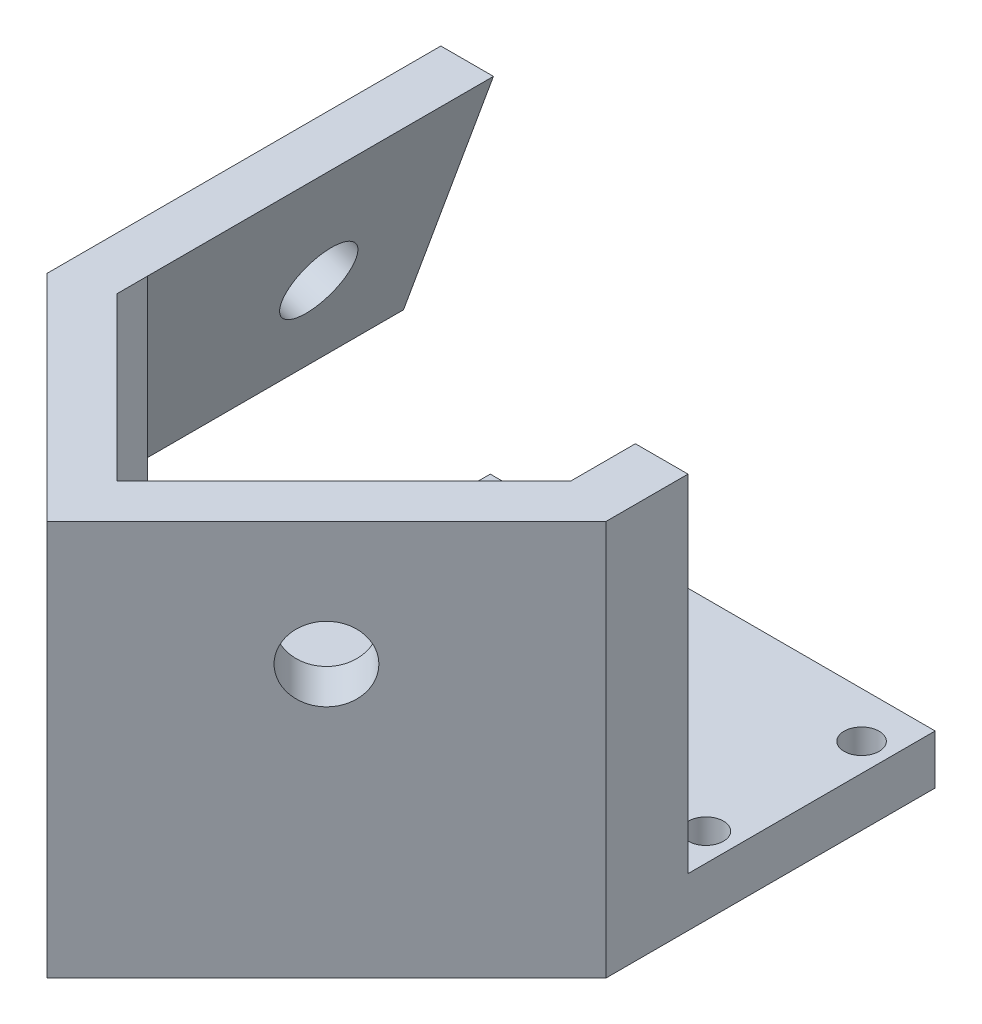
SolidWorks part; units mm, degrees
material "PLA Grey"
ref_plane "Front Plane" through (0, 0, 0) normal (0, 0, 1) x (1, 0, 0)
ref_plane "Top Plane" through (0, 0, 0) normal (0, 1, 0) x (1, 0, 0)
ref_plane "Right Plane" through (0, 0, 0) normal (1, 0, 0) x (0, 0, -1)
sketch "Sketch1" plane through (0, 0, 0) normal (0, 1, 0) x (1, 0, 0)
  line L0 (-35.921, 0) -> (0, 35.921)
  line L1 (-35.921, 0) -> (0, -35.921)
  line L2 (0, 35.921) -> (35.921, 0)
  line L3 (0, -35.921) -> (35.921, 0)
  line L4 (-35.921, 0) -> (35.921, 0) construction
  line L5 (0, 35.921) -> (0, -35.921) construction
  point P1 (0, 0)
  dimension "D1" = 50.8
  dimension "D2" = 50.8
extrude "Boss-Extrude1" add sketch "Sketch1" along normal mid plane 31.75
sketch "Sketch2" plane through (17.9605, 0, 17.9605) normal (0.7071, 0, 0.7071) x (0.7071, 0, -0.7071)
  circle A0 centre (0, 0) radius 4.7625
  dimension "D1" = 9.525
extrude "Cut-Extrude1" cut sketch "Sketch2" against normal blind 8
sketch "Sketch3" plane through (-17.9605, 0, 17.9605) normal (-0.7071, 0, 0.7071) x (0.7071, 0, 0.7071)
  circle A0 centre (0, 0) radius 4.7625
  dimension "D1" = 9.525
extrude "Cut-Extrude2" cut sketch "Sketch3" against normal blind 8
sketch "Sketch4" plane through (0, 15.875, 0) normal (0, 1, 0) x (1, 0, 0)
  line L0 (25.4, 10.521) -> (-25.4, 10.521)
  line L1 (35.921, 0) -> (0, 35.921) construction
  line L2 (0, 35.921) -> (-35.921, 0) construction
  line L3 (-25.4, 10.521) -> (0, 35.921)
  line L4 (0, 35.921) -> (25.4, 10.521)
  dimension "D1" = 25.4
extrude "Cut-Extrude3" cut sketch "Sketch4" against normal through all
sketch "Sketch5" plane through (0, 0, -10.521) normal (0, 0, -1) x (-1, 0, 0)
  line L0 (-35.921, 15.875) -> (-35.921, -15.875)
  line L1 (-35.921, -15.875) -> (39.135, -15.875)
  line L2 (39.135, -15.875) -> (27.579, 15.875)
  line L3 (27.579, 15.875) -> (-35.921, 15.875)
  line L4 (25.4, -15.875) -> (-25.4, -15.875) construction
  line L5 (-35.921, 15.875) -> (-35.921, -15.875) construction
  line L8 (25.4, 15.875) -> (-25.4, 15.875) construction
  point P6 (0, 0)
  dimension "D1" = 70
  dimension "D2" = 63.5
extrude "Boss-Extrude2" add sketch "Sketch5" against normal up to surface and the other way blind 31.75 up to face at (30.6605, 0, -5.2605)
sketch "Sketch6" plane through (-29.455, 10.7207, 0) normal (-0.9397, 0.342, 0) x (0, 0, 1)
  line L0 (-42.271, -28.3026) -> (-42.271, 5.4851) construction
  line L1 (-42.271, -28.3026) -> (-10.521, -28.3026) construction
  circle A0 centre (-26.396, -11.4088) radius 4.7625
  point P4 (-42.271, -11.4088)
  point P7 (-26.396, -28.3026)
  dimension "D1" = 9.525
extrude "Cut-Extrude4" cut sketch "Sketch6" against normal through all
sketch "Sketch7" plane through (0, 0, -42.271) normal (0, 0, -1) x (-1, 0, 0)
  line L1 (-35.921, -15.875) -> (39.135, -15.875) construction
  line L3 (20.8214, 15.875) -> (32.3775, -15.875)
  line L4 (-35.921, -15.875) -> (32.3775, -15.875)
  line L5 (39.135, -15.875) -> (27.579, 15.875) construction
  line L6 (27.579, 15.875) -> (-35.921, 15.875) construction
  line L7 (-35.921, -15.875) -> (-35.921, 15.875)
  line L8 (-35.921, 15.875) -> (20.8214, 15.875)
  dimension "D3" = 6.35
extrude "Cut-Extrude5" cut sketch "Sketch7" against normal blind 31.75
sketch "Sketch8" plane through (0, 15.875, 0) normal (0, 1, 0) x (1, 0, 0)
  line L5 (-42.1413, -6.2203) -> (-8.2965, -39.8855)
  line L6 (0, -35.921) -> (0, -57.0039)
  line L13 (0, -57.0039) -> (-46.5861, -10.6651)
  line L14 (-46.5861, -10.6651) -> (-42.1413, -6.2203)
  line L15 (-8.2965, -39.8855) -> (-8.2965, -27.6245)
  line L16 (-35.921, 0) -> (0, -35.921) construction
  line L17 (-8.2965, -27.6245) -> (0, -35.921)
  line L18 (-25.4, 10.521) -> (-35.921, 0) construction
extrude "Boss-Extrude3" [suppressed] add sketch "Sketch8" against normal up to surface (25.4 mm away)
sketch "Sketch9" plane through (0, -15.875, 0) normal (0, -1, 0) x (1, 0, 0)
  line L0 (-25.4, -10.521) -> (-35.921, 0)
  line L1 (-35.921, 0) -> (-46.442, -10.521)
  line L2 (-46.442, -10.521) -> (-25.4, -10.521)
  line L3 (-35.921, 0) -> (0, 35.921) construction
extrude "Boss-Extrude4" add sketch "Sketch9" against normal up to surface (31.75 mm away) up to face at (-9.5866, 15.875, -10.0783)
sketch "Sketch10" plane through (0, 0, -42.271) normal (0, 0, -1) x (-1, 0, 0)
  line L0 (39.135, -15.875) -> (27.579, 15.875) construction
  line L1 (39.135, -15.875) -> (27.579, 15.875)
  line L6 (27.579, 15.875) -> (39.135, -15.875)
  line L7 (39.135, -15.875) -> (46.442, -15.875)
  line L8 (46.442, -15.875) -> (46.442, 15.875)
  line L9 (46.442, 15.875) -> (27.579, 15.875)
  line L10 (27.579, 15.875) -> (39.135, -15.875)
  line L11 (39.135, -15.875) -> (46.442, -15.875)
  line L12 (46.442, -15.875) -> (46.442, 15.875)
  line L13 (46.442, 15.875) -> (27.579, 15.875)
  line M7 (39.135, -15.875) -> (27.579, 15.875)
  dimension "D1" = 0
extrude "Cut-Extrude6" cut sketch "Sketch10" against normal through all contours L12 L13 L11 M7 region at (-39.4743, 2.3367, -42.271)
sketch "Sketch11" plane through (0, -15.875, 0) normal (0, -1, 0) x (1, 0, 0)
  line L3 (-32.3775, -10.521) -> (-39.135, -10.521)
  line L4 (-39.135, -42.271) -> (-39.135, -3.214) construction
  line L5 (-39.135, -10.521) -> (-39.135, -3.214)
  line L10 (0, 35.921) -> (-39.135, -3.214)
  line L11 (-39.135, -3.214) -> (-39.135, -42.271)
  line L12 (-39.135, -42.271) -> (-32.3775, -42.271)
  line L13 (-32.3775, -42.271) -> (-32.3775, -10.521)
  line L21 (-32.3775, -10.521) -> (35.921, -10.521)
  line L22 (35.921, -10.521) -> (35.921, 0)
  line L23 (35.921, 0) -> (0, 35.921)
  line L24 (0, 35.921) -> (-39.135, -3.214)
  line L30 (35.921, -10.521) -> (35.921, 0)
  line L31 (35.921, 0) -> (0, 35.921)
  line L34 (-32.3775, -10.521) -> (35.921, -10.521)
  dimension "D1" = 0
extrude "Boss-Extrude5" add sketch "Sketch11" along normal blind 12.7
sketch "Sketch12" plane through (0, -28.575, 0) normal (0, -1, 0) x (1, 0, 0)
  line L0 (35.921, -10.521) -> (35.921, 0)
  line L1 (35.921, 0) -> (0, 35.921)
  line L2 (0, 35.921) -> (-39.135, -3.214)
  line L3 (-39.135, -3.214) -> (-39.135, -42.271)
  line L4 (-39.135, -42.271) -> (35.921, -42.271)
  line L5 (35.921, -42.271) -> (35.921, -10.521)
extrude "Boss-Extrude6" add sketch "Sketch12" along normal blind 6.35
sketch "Sketch14" plane through (0, 0, -10.521) normal (0, 0, -1) x (-1, 0, 0)
  line L0 (36.9999, -28.575) -> (20.8214, 15.875)
  line L1 (39.135, -34.925) -> (21.229, -34.925)
  line L2 (20.8214, 15.875) -> (5.0505, 15.875)
  line L3 (21.229, -28.575) -> (5.0505, 15.875)
  line L4 (20.8214, 15.875) -> (-35.921, 15.875) construction
  line L5 (32.3775, -15.875) -> (20.8214, 15.875) construction
  line L6 (39.135, -34.925) -> (-35.921, -34.925) construction
  line L7 (39.135, -34.925) -> (39.135, -28.575)
  line L8 (39.135, -28.575) -> (36.9999, -28.575)
  line L9 (21.229, -28.575) -> (21.229, -34.925)
  line L11 (39.135, -28.575) -> (-35.921, -28.575) construction
  line L12 (-35.921, -34.925) -> (-35.921, -28.575) construction
  dimension "D1" = 57.15
extrude "Cut-Extrude7" cut sketch "Sketch14" along normal through all
sketch "Sketch15" plane through (0, -34.925, 0) normal (0, -1, 0) x (1, 0, 0)
  line L0 (-21.229, -42.271) -> (35.921, -42.271) construction
  line L1 (32.346, -16.396) -> (-17.654, -16.396) construction
  line L2 (32.346, -16.396) -> (32.346, -36.396) construction
  line L3 (32.346, -36.396) -> (-17.654, -36.396) construction
  line L4 (-17.654, -16.396) -> (-17.654, -36.396) construction
  line L5 (32.346, -16.396) -> (-17.654, -36.396) construction
  line L6 (32.346, -36.396) -> (-17.654, -16.396) construction
  line L9 (-21.229, -42.271) -> (-21.229, -10.521) construction
  circle A0 centre (32.346, -36.396) radius 2.25
  circle A1 centre (32.346, -16.396) radius 2.25
  circle A2 centre (-17.654, -16.396) radius 2.25
  circle A3 centre (-17.654, -36.396) radius 2.25
  point P0 (7.346, -26.396)
  point P11 (7.346, -42.271)
  point P14 (-21.229, -26.396)
  dimension "D1" = 4.5
  dimension "D2" = 50
  dimension "D3" = 20
extrude "Cut-Extrude8" cut sketch "Sketch15" against normal up to next
sketch "Sketch17" plane through (0, 15.875, 0) normal (0, 1, 0) x (1, 0, 0)
  line L0 (-20.8214, 10.521) -> (-20.8214, -6.1193)
  line L1 (-20.8214, -6.1193) -> (0, -26.9408)
  line L2 (0, -26.9408) -> (29.1635, 2.2227)
  line L3 (29.1635, 2.2227) -> (29.1635, 10.521)
  line L4 (-20.8214, 10.521) -> (35.921, 10.521) construction
  line L5 (14.5817, -12.359) -> (19.0719, -16.8491) construction
  line L6 (0, -35.921) -> (35.921, 0) construction
  line L7 (-10.4107, -16.53) -> (-14.9009, -21.0202) construction
  line L8 (-27.579, -8.342) -> (0, -35.921) construction
  line L9 (29.1635, 10.521) -> (35.921, 10.521) construction
  line L10 (-20.8214, 10.521) -> (-27.579, 10.521) construction
  line L11 (-27.579, 42.271) -> (-27.579, -8.342) construction
  line L12 (-20.8214, 10.521) -> (29.1635, 10.521)
  dimension "D1" = 6.35
extrude "Cut-Extrude9" cut sketch "Sketch17" against normal up to surface (44.45 mm away) up to face at (-17.654, -28.575, -34.146)
sketch "Sketch20" plane through (0, 0, -10.521) normal (0, 0, -1) x (-1, 0, 0)
  line L7 (32.3775, -15.875) -> (20.8214, 15.875)
  line L8 (20.8214, 15.875) -> (20.8214, -28.575)
  line L9 (20.8214, -28.575) -> (21.229, -28.575)
  line L10 (21.229, -28.575) -> (21.229, -34.925)
  line L11 (21.229, -28.575) -> (21.229, -34.925)
  line L12 (39.135, -34.925) -> (39.135, -15.875)
  line L14 (32.3775, -15.875) -> (20.8214, 15.875)
  line L16 (20.8214, -28.575) -> (21.229, -28.575)
  line L19 (39.135, -34.925) -> (39.135, -15.875)
  line L21 (21.229, -34.925) -> (39.135, -34.925)
  line L22 (21.229, -34.925) -> (39.135, -34.925)
  line L23 (20.8214, 15.875) -> (20.8214, -28.575)
  line L24 (39.135, -15.875) -> (32.3775, -15.875)
  line L26 (39.135, -15.875) -> (32.3775, -15.875)
  dimension "D1" = 0
extrude "Cut-Extrude10" cut sketch "Sketch20" against normal blind 12.7
sketch "Sketch21" plane through (0, 0, 2.179) normal (0, 0, -1) x (-1, 0, 0)
  line L0 (21.229, -28.575) -> (21.229, -34.925) construction
  line L1 (33.742, -34.925) -> (21.229, -34.925)
  line L2 (33.742, -34.925) -> (33.742, -15.875)
  line L3 (33.742, -15.875) -> (21.229, -15.875)
  line L4 (21.229, -34.925) -> (21.229, -15.875)
  line L5 (33.742, -15.875) -> (32.3775, -15.875) construction
extrude "Cut-Extrude11" cut sketch "Sketch21" against normal through all
